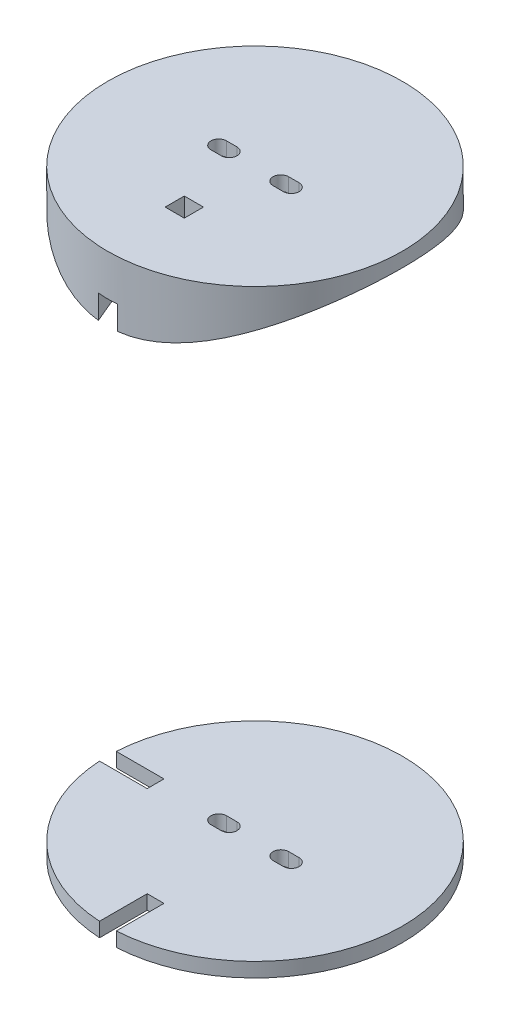
SolidWorks part; units mm, degrees
ref_plane "Спереди" through (0, 0, 0) normal (0, 0, 1) x (1, 0, 0)
ref_plane "Сверху" through (0, 0, 0) normal (0, 1, 0) x (1, 0, 0)
ref_plane "Справа" through (0, 0, 0) normal (1, 0, 0) x (0, 0, -1)
sketch "Эскиз1" plane through (0, 0, 0) normal (0, 1, 0) x (1, 0, 0)
  line L0 (-67.8442, 0) -> (118.5668, 0) construction
  line L1 (-15.15, 0) -> (-10.8, 0) construction
  line L2 (-15.15, 3.25) -> (-10.8, 3.25)
  line L3 (-15.15, -3.25) -> (-10.8, -3.25)
  line L4 (0, 40.4544) -> (0, -45.9806) construction
  line L5 (15.15, 0) -> (10.8, 0) construction
  line L6 (15.15, 3.25) -> (10.8, 3.25)
  line L7 (15.15, -3.25) -> (10.8, -3.25)
  line L8 (-3.5, -61.4003) -> (-3.5, -41.5)
  line L9 (-3.5, -41.5) -> (3.5, -41.5)
  line L10 (3.5, -41.5) -> (3.5, -61.4003)
  line L11 (-61.4003, 3.5) -> (-41.5, 3.5)
  line L12 (-41.5, 3.5) -> (-41.5, -3.5)
  line L13 (-41.5, -3.5) -> (-61.4003, -3.5)
  circle A0 centre (0, 0) radius 61.5
  arc A1 (-15.15, 3.25) -> (-15.15, -3.25) centre (-15.15, 0) ccw
  arc A2 (-10.8, -3.25) -> (-10.8, 3.25) centre (-10.8, 0) ccw
  arc A3 (15.15, 3.25) -> (15.15, -3.25) centre (15.15, 0) cw
  arc A4 (10.8, -3.25) -> (10.8, 3.25) centre (10.8, 0) cw
  point P7 (-12.975, 0)
  point P16 (12.975, 0)
  point P26 (0, -41.5)
  point P30 (-41.5, 0)
  point P31 (3.5, -61.4003)
  dimension "D1" = 123
  dimension "D2" = 15.1
  dimension "D3" = 36.8
  dimension "D5" = 20
  dimension "D4" = 6.5
  dimension "D6" = 7
extrude "Бобышка-Вытянуть1" add sketch "Эскиз1" along normal blind 6 contours L13 A0 L11 L12 A2 L3 A1 L2 L7 A4 L6 A3 region at (0.6268, 0, -0.6268)
extrude "Бобышка-Вытянуть2" add sketch "Эскиз1<3>" along normal blind 100 from offset 150 separate body contours L10 A0 L11 L12 L13 L8 L9 A2 L3 A1 L2 L7 A4 L6 A3 | L8 A0 L10 L9 | L11 A0 L13 L12 region at (0.6268, 0, -0.6268) region at (0, 0, 51.4834) region at (-51.4834, 0, 0)
sketch "Эскиз1<3>" plane through (0, 0, 0) normal (0, 1, 0) x (1, 0, 0) same geometry as "Эскиз1"
sketch "Эскиз3" plane through (0, 0, 0) normal (1, 0, 0) x (0, 0, -1)
  line L1 (61.5, 250) -> (-61.5, 250) construction
  line L2 (-61.5, 250) -> (-61.5, 150) construction
  line L3 (61.5, 250) -> (-61.5, 250)
  line L5 (-61.5, 250) -> (-61.5, 150)
  line L6 (-25.5156, 250) -> (-25.5156, 240.69)
  line L7 (-33.5156, 246.6679) -> (-33.5156, 250)
  circle A0 centre (0, 144) radius 100
  arc A1 (-33.5156, 246.6679) -> (-61.5, 232.7792) centre (0, 144) ccw
  point P6 (-33.5156, 246.6679)
  point P12 (-24.5995, 240.9271)
  point P13 (-33.6135, 246.1094)
  dimension "D1" = 200
  dimension "D2" = 6
  dimension "D5" = 8
  dimension "D4" = 8
extrude "Вырез-Вытянуть1" cut sketch "Эскиз3" against normal through all both and the other way through all contours A0 region at (0, 144, 0)
extrude "Вырез-Вытянуть2" cut sketch "Эскиз3<3>" against normal mid plane 8 contours L7 A1 L5 A0 L6 L3 region at (0, 238.0544, 43.3529)
sketch "Эскиз3<3>" plane through (0, 0, 0) normal (1, 0, 0) x (0, 0, -1) same geometry as "Эскиз3"
